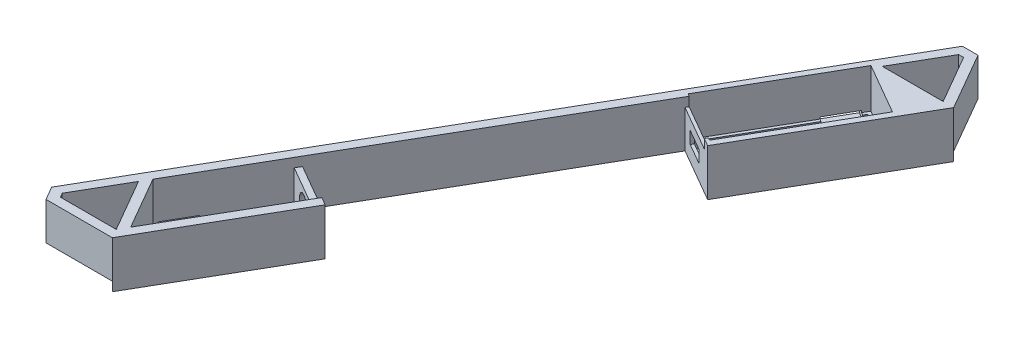
SolidWorks part; units mm, degrees
ref_plane "Front Plane" through (0, 0, 0) normal (0, 0, 1) x (1, 0, 0)
ref_plane "Top Plane" through (0, 0, 0) normal (0, 1, 0) x (1, 0, 0)
ref_plane "Right Plane" through (0, 0, 0) normal (1, 0, 0) x (0, 0, -1)
sketch "Sketch1" plane through (0, 0, 0) normal (0, 1, 0) x (1, 0, 0)
  line L24 (-11.7321, 167.8653) -> (3.2679, 159.2051)
  line L29 (3.2679, 159.2051) -> (-18.2321, 121.966) construction
  line L31 (-107.8246, -1.4282) -> (-108.6491, 0)
  line L40 (-0.8246, 186.7576) -> (0.8246, 186.7576)
  line L41 (-109.5566, -4.4282) -> (-112.1132, 0)
  line L42 (-2.5566, 189.7576) -> (-112.1132, 0)
  line L44 (-2.5566, 189.7576) -> (2.5566, 189.7576)
  line L50 (-99.4737, 15.8923) -> (-89.4737, -1.4282)
  line L51 (-107.8246, -1.4282) -> (-89.4737, -1.4282)
  line L52 (-99.4737, 15.8923) -> (-108.6491, 0)
  line L62 (-10, 170.8653) -> (10, 170.8653)
  line L63 (-10, 170.8653) -> (-0.8246, 186.7576)
  line L64 (0.8246, 186.7576) -> (10, 170.8653)
  line L65 (2.5566, 189.7576) -> (13.4641, 170.8653)
  line L71 (-109.5566, -4.4282) -> (-87.7417, -4.4282)
  line L82 (-39.7369, 84.7186) -> (-37.1388, 83.2186)
  line L96 (13.4641, 170.8653) -> (-16.134, 119.6)
  line L100 (-18.2321, 121.966) -> (-33.2321, 130.6262)
  line L102 (-11.7321, 167.8653) -> (-33.2321, 130.6262)
  line L104 (-33.7321, 129.7602) -> (-97.7417, 18.8923)
  line L111 (-33.7321, 129.7602) -> (-18.7321, 121.1)
  line L113 (-16.134, 119.6) -> (-18.7321, 121.1)
  line L115 (-18.7321, 121.1) -> (-18.2321, 121.966)
  line L117 (-18.2321, 121.966) -> (3.2679, 159.2051)
  line L119 (-33.7321, 129.7602) -> (-33.2321, 130.6262)
  line L121 (-97.7417, 18.8923) -> (-80.7417, 48.3372) construction
  line L123 (-80.7417, 48.3372) -> (-65.7417, 39.6769)
  line L127 (-82.7417, 10.2321) -> (-65.7417, 39.6769)
  line L133 (-65.7417, 39.6769) -> (-64.7417, 41.409)
  line L134 (-64.7417, 41.409) -> (-79.7417, 50.0692)
  line L135 (-64.7417, 41.409) -> (-62.1436, 39.909)
  line L137 (-87.7417, -4.4282) -> (-62.1436, 39.909)
  line L138 (-97.7417, 18.8923) -> (-87.7417, 1.5718)
  line L141 (-82.7417, 10.2321) -> (-87.7417, 1.5718)
  dimension "D1" = 43
  dimension "D2" = 34
  dimension "D3" = 2
extrude "Boss-Extrude2" add sketch "Sketch1" along normal blind 15.38 contours L41 L71 L65 L44 L42 L40 L64 L62 L63 L52 L50 L51 L31 region at (-24.4848, 0, -150.4021)
extrude "Boss-Extrude3" add sketch "Sketch1<11>" along normal blind 1 contours L24 L102 L100 | L127 L123 L104 region at (-14.9821, 0, -144.9157) region at (-82.7246, 0, -26.842)
sketch "Sketch1<11>" plane through (0, 0, 0) normal (0, 1, 0) x (1, 0, 0) same geometry as "Sketch1"
extrude "Boss-Extrude4" add sketch "Sketch1<12>" along normal blind 12.38 contours L119 L111 L115 L100 | L133 L134 L104 L123 region at (-25.9821, 0, -125.8631) region at (-72.7417, 0, -44.8731)
sketch "Sketch1<12>" plane through (0, 0, 0) normal (0, 1, 0) x (1, 0, 0) same geometry as "Sketch1"
sketch "Sketch10" plane through (47.7548, 0, -82.7138) normal (-0.5, 0, 0.866) x (0.866, 0, 0.5)
  line L0 (-94.0929, 0) -> (-85.4329, 0) construction
  line L1 (-73.7724, 0) -> (-94.0929, 0) construction
  line L2 (-85.4329, 0) -> (-85.4329, 5) construction
  line L3 (-85.4329, 5) -> (-81.4329, 5)
  line L4 (-85.4329, 5) -> (-89.4329, 5)
  line L5 (-81.4329, 5) -> (-81.4329, 9)
  line L6 (-89.4329, 5) -> (-89.4329, 9)
  line L7 (-89.4329, 9) -> (-81.4329, 9)
extrude "Cut-Extrude1" cut sketch "Sketch10" against normal blind 8.26
sketch "Sketch12" plane through (1.7452, 0, -3.0228) normal (0.5, 0, -0.866) x (-0.866, 0, -0.5)
  line L0 (94.0929, 0) -> (85.4329, 0) construction
  line L1 (94.0929, 0) -> (73.7724, 0) construction
  line L2 (85.4329, 0) -> (85.4329, 2.5) construction
  line L3 (85.4329, 2.5) -> (85.4329, 6.5) construction
  circle A0 centre (85.4329, 6.5) radius 4
extrude "Cut-Extrude2" cut sketch "Sketch12" against normal blind 8.26
sketch "Sketch15" plane through (0, 0, 0) normal (0, -1, 0) x (1, 0, 0)
  line L0 (-87.7417, 4.4282) -> (-109.5566, 4.4282)
  line L1 (-109.5566, 4.4282) -> (-112.1132, 0)
  line L2 (-112.1132, 0) -> (-101.2058, -18.8923)
  line L3 (-87.7417, 4.4282) -> (-101.2058, -18.8923)
  line L4 (13.4641, -170.8653) -> (2.5566, -189.7576)
  line L5 (2.5566, -189.7576) -> (-2.5566, -189.7576)
  line L6 (-13.4641, -170.8653) -> (-2.5566, -189.7576)
  line L7 (13.4641, -170.8653) -> (-13.4641, -170.8653)
extrude "Cut-Extrude3" cut sketch "Sketch15" against normal blind 3
sketch "Sketch16" plane through (-84.0849, 0, -48.5465) normal (-0.866, 0, -0.5) x (-0.5, 0, 0.866)
  line L0 (-163.0566, 3) -> (-138.2426, 3) construction
  line L1 (56.0566, 3) -> (31.2426, 3) construction
  line L2 (-138.2426, 3) -> (-128.2426, 3)
  line L3 (-138.2426, 3) -> (-138.2426, 1)
  line L4 (-138.2426, 1) -> (-128.2426, 1)
  line L5 (-128.2426, 3) -> (-128.2426, 1)
  line L6 (31.2426, 3) -> (31.2426, 1)
  line L11 (31.2426, 1) -> (21.2426, 1)
  line L12 (21.2426, 1) -> (21.2426, 3)
  line L13 (21.2426, 3) -> (31.2426, 3)
extrude "Cut-Extrude4" cut sketch "Sketch16" against normal blind 3
sketch "Sketch17" plane through (0, 15.38, 0) normal (0, 1, 0) x (1, 0, 0)
  line L0 (-18.2321, 121.966) -> (-17.366, 121.466)
  line L1 (4.634, 159.5711) -> (-17.366, 121.466)
  line L3 (-33.2321, 130.6262) -> (-34.0981, 131.1262)
  line L4 (-33.2321, 130.6262) -> (-18.2321, 121.966)
  line L5 (-12.0981, 169.2314) -> (4.634, 159.5711)
  line L7 (-34.0981, 131.1262) -> (-12.0981, 169.2314)
extrude "Cut-Extrude5" cut sketch "Sketch17" against normal blind 13
sketch "Sketch18" plane through (0, 0, 0) normal (0, -1, 0) x (1, 0, 0)
  line L0 (-18.2321, -121.966) -> (3.2679, -159.2051)
  line L1 (3.2679, -159.2051) -> (-11.7321, -167.8653)
  line L2 (-11.7321, -167.8653) -> (-33.2321, -130.6262)
  line L3 (-33.2321, -130.6262) -> (-18.2321, -121.966)
extrude "Cut-Extrude6" cut sketch "Sketch18" against normal blind 1
